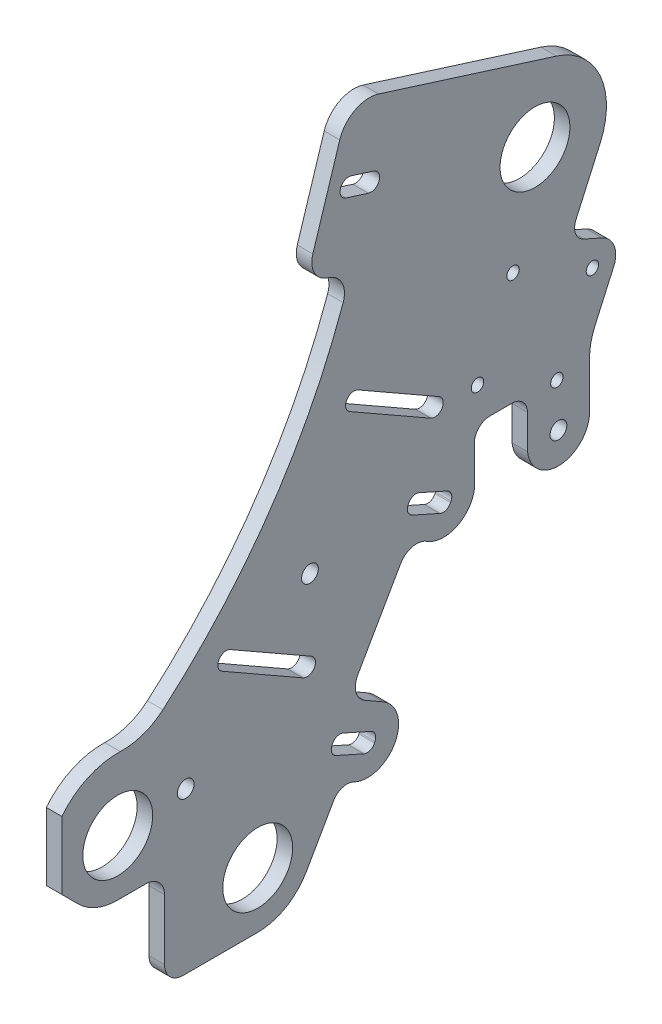
SolidWorks part; units mm, degrees
ref_plane "Front Plane" through (0, 0, 0) normal (0, 0, 1) x (1, 0, 0)
ref_plane "Top Plane" through (0, 0, 0) normal (0, 1, 0) x (1, 0, 0)
ref_plane "Right Plane" through (0, 0, 0) normal (1, 0, 0) x (0, 0, -1)
sketch "Sketch1" plane through (0, 0, 0) normal (1, 0, 0) x (0, 0, -1)
  line L0 (0, 0) -> (-57.2178, 40.0643) construction
  line L1 (55, 0) -> (-55, 0) construction
  line L2 (0, 0) -> (113.3671, 198.5091) construction
  line L3 (113.3671, 198.5091) -> (49.679, 218.5899) construction
  line L4 (99.338, 182.3162) -> (24.13, 14.224) construction
  line L5 (30.5555, 28.5852) -> (30.3602, 28.1486)
  line L6 (36.1341, 219.132) -> (45.2183, 216.2678)
  line L7 (38.2727, 225.9148) -> (47.3569, 223.0506)
  line L8 (34.9378, 30.2582) -> (46.2714, 25.1873)
  line L9 (47.9444, 20.8051) -> (47.749, 20.3685)
  line L10 (43.3668, 18.6955) -> (32.0332, 23.7664)
  line L11 (104.397, 158.4994) -> (136.8574, 143.9792) construction
  line L12 (136.8574, 143.9792) -> (122.3372, 111.5188) construction
  line L14 (61.6761, 98.1406) -> (61.4807, 97.704)
  line L15 (66.0583, 99.8136) -> (77.3919, 94.7427)
  line L16 (79.0649, 90.3605) -> (78.8696, 89.9239)
  line L17 (74.4873, 88.2509) -> (63.1537, 93.3218)
  line L18 (72.429, 126.8253) -> (39.3441, 145.7198) construction
  line L19 (20.2106, 60.9985) -> (-12.8742, 79.893) construction
  line L20 (70.7285, 123.8476) -> (37.6436, 142.7421)
  line L21 (74.1295, 129.8029) -> (41.0446, 148.6974)
  line L22 (18.5101, 58.0208) -> (-14.5747, 76.9153)
  line L23 (122.3372, 111.5188) -> (89.8768, 126.039) construction
  line L24 (89.8768, 126.039) -> (104.397, 158.4994) construction
  line L25 (104.397, 158.4994) -> (122.3372, 111.5188) construction
  line L26 (21.9112, 63.9761) -> (-11.1737, 82.8706)
  circle A0 centre (0, 0) radius 14.2875
  circle A1 centre (-57.2178, 40.0643) radius 14.2875
  circle A2 centre (113.3671, 198.5091) radius 14.2875
  arc A3 (45.2183, 216.2678) -> (47.3569, 223.0506) centre (46.2876, 219.6592) ccw
  arc A4 (38.2727, 225.9148) -> (36.1341, 219.132) centre (37.2034, 222.5234) ccw
  arc A17 (46.2714, 25.1873) -> (47.9444, 20.8051) centre (44.9167, 22.1597) cw
  arc A18 (47.749, 20.3685) -> (43.3668, 18.6955) centre (44.7214, 21.7231) cw
  arc A19 (32.0332, 23.7664) -> (30.3602, 28.1486) centre (33.3878, 26.794) cw
  arc A20 (30.5555, 28.5852) -> (34.9378, 30.2582) centre (33.5831, 27.2306) cw
  arc A21 (74.4873, 88.2509) -> (78.8696, 89.9239) centre (75.842, 91.2785) ccw
  arc A22 (79.0649, 90.3605) -> (77.3919, 94.7427) centre (76.0373, 91.7151) ccw
  arc A23 (63.1537, 93.3218) -> (61.4807, 97.704) centre (64.5084, 96.3494) cw
  arc A24 (61.6761, 98.1406) -> (66.0583, 99.8136) centre (64.7037, 96.786) cw
  circle A25 centre (-29.4365, 42.7262) radius 3.429
  circle A26 centre (21.3635, 93.5262) radius 3.429
  circle A27 centre (122.9635, 93.5262) radius 3.429
  arc A28 (70.7285, 123.8476) -> (74.1295, 129.8029) centre (72.429, 126.8253) ccw
  arc A29 (41.0446, 148.6974) -> (37.6436, 142.7421) centre (39.3441, 145.7198) ccw
  circle A32 centre (104.397, 158.4994) radius 2.54
  circle A33 centre (136.8574, 143.9792) radius 2.54
  circle A34 centre (122.3372, 111.5188) radius 2.54
  circle A35 centre (89.8768, 126.039) radius 2.54
  arc A36 (18.5101, 58.0208) -> (21.9112, 63.9761) centre (20.2106, 60.9985) ccw
  arc A37 (-11.1737, 82.8706) -> (-14.5747, 76.9153) centre (-12.8742, 79.893) ccw
  point P30 (113.3671, 135.0091)
  point P36 (3.6682, 70.4457)
  point P44 (0, 0)
  point P45 (0, 0)
  point P47 (49.299, 23.8327)
  point P54 (29.0056, 25.121)
  point P57 (31.9101, 31.6128)
  point P62 (80.4195, 93.3881)
  point P65 (60.1261, 94.6764)
  point P68 (63.0307, 101.1682)
  point P78 (55.8866, 136.2725)
  dimension "D2" = 28.575
  dimension "D4" = 228.6
  dimension "D10" = 13.081
  dimension "D7" = 3.556
  dimension "D8" = 9.525
  dimension "D11" = 65.895
  dimension "D18" = 35.56
  dimension "D20" = 38.1
  dimension "D21" = 24.1
  dimension "D27" = 7.112
  dimension "D22" = 5.08
  dimension "D29" = 3.3168
  dimension "D30" = 6.858
  dimension "D33" = 6.858
  dimension "D36" = 6.858
  dimension "D40" = 3.429
  dimension "D25" = 3.429
  dimension "D26" = 50.8
  dimension "D1" = 35
  dimension "D3" = 69.85
  dimension "D5" = 60.27
  dimension "D6" = 17.5
  dimension "D9" = 66.7788
  dimension "D12" = 14.224
  dimension "D13" = 184.15
  dimension "D14" = 24.13
  dimension "D15" = 7.112
  dimension "D16" = 165.1
  dimension "D17" = 19.05
  dimension "D19" = 63.5
  dimension "D23" = 19.05
  dimension "D24" = 76.2
  dimension "D28" = 88.9
  dimension "D31" = 27.7812
  dimension "D32" = 2.6619
  dimension "D34" = 78.5812
  dimension "D35" = 53.4619
  dimension "D37" = 180.1812
  dimension "D38" = 53.4619
  dimension "D39" = 82.55
  dimension "D41" = 38.1
sketch "Sketch2" plane through (0, 0, 0) normal (1, 0, 0) x (0, 0, -1)
  line L1 (-80.0778, 30.5954) -> (-80.0778, 58.2479)
  line L2 (19.8509, -11.3367) -> (31.0118, 8.2063)
  line L3 (0, 0) -> (113.3671, 198.5091) construction
  line L9 (113.3671, 198.5091) -> (49.679, 218.5899) construction
  line L11 (49.4775, 249.281) -> (122.1507, 226.3672)
  line L12 (33.5463, 240.9877) -> (22.5477, 206.1046)
  line L13 (28.5188, 194.6341) -> (29.0827, 194.4563)
  line L14 (110.3329, 92.1997) -> (110.288, 92.1997)
  line L15 (88.5941, 92.1997) -> (88.5941, 106.1697)
  line L16 (110.288, 92.1997) -> (110.288, 106.1697)
  line L17 (103.938, 112.5197) -> (94.9441, 112.5197)
  line L18 (88.5941, 92.1997) -> (88.5941, 89.8131)
  line L19 (58.4048, 78.4274) -> (40.9124, 47.8643)
  line L20 (43.7407, 37.4658) -> (51.2253, 33.1821)
  line L23 (-38.1, 9.5843) -> (-38.1, -15.24)
  line L24 (-30.48, -22.86) -> (0, -22.86)
  line L25 (-57.2178, 17.2043) -> (-45.72, 17.2043)
  line L26 (-73.3822, 23.8999) -> (-80.0778, 30.5954)
  line L27 (104.397, 158.4994) -> (136.8574, 143.9792) construction
  line L28 (136.8574, 143.9792) -> (122.3372, 111.5188) construction
  line L29 (122.3372, 111.5188) -> (89.8768, 126.039) construction
  line L30 (89.8768, 126.039) -> (104.397, 158.4994) construction
  line L31 (104.397, 158.4994) -> (122.3372, 111.5188) construction
  line L32 (140.031, 186.5818) -> (130.1045, 164.3908)
  line L33 (140.7468, 152.6739) -> (133.3081, 156.0014)
  line L34 (145.5521, 140.0898) -> (137.8775, 122.9329)
  line L35 (135.6635, 93.5262) -> (135.6635, 112.5613)
  arc A1 (0, -22.86) -> (19.8509, -11.3367) centre (0, 0) ccw
  arc A2 (39.3228, 10.758) -> (51.2253, 33.1821) centre (44.9167, 22.1597) ccw
  arc A3 (69.1503, 81.0446) -> (88.5941, 89.8131) centre (76.0373, 91.7151) ccw
  arc A7 (31.0118, 8.2063) -> (39.3228, 10.758) centre (36.5259, 5.0572) cw
  arc A13 (140.031, 186.5818) -> (122.1507, 226.3672) centre (113.3671, 198.5091) ccw
  arc A15 (33.5463, 240.9877) -> (49.4775, 249.281) centre (45.6585, 237.1687) cw
  arc A16 (34.9451, 182.6622) -> (-38.7381, 75.3772) centre (-204.3307, 268.0513) cw
  arc A17 (-56.1886, 69.2562) -> (-80.0778, 58.2479) centre (-57.2178, 40.0643) ccw
  arc A18 (29.0827, 194.4563) -> (34.9451, 182.6622) centre (26.3331, 185.7355) cw
  arc A19 (22.5477, 206.1046) -> (28.5188, 194.6341) centre (31.2685, 203.3549) ccw
  arc A21 (-38.7381, 75.3772) -> (-56.1886, 69.2562) centre (-55.2938, 94.6404) cw
  arc A22 (110.3329, 92.1997) -> (135.6635, 93.5262) centre (122.9635, 93.5262) ccw
  arc A25 (110.288, 106.1697) -> (103.938, 112.5197) centre (103.938, 106.1697) ccw
  arc A26 (88.5941, 106.1697) -> (94.9441, 112.5197) centre (94.9441, 106.1697) cw
  arc A27 (58.4048, 78.4274) -> (69.1503, 81.0446) centre (65.0182, 74.6423) cw
  arc A28 (43.7407, 37.4658) -> (40.9124, 47.8643) centre (47.5258, 44.0792) cw
  arc A29 (-73.3822, 23.8999) -> (-57.2178, 17.2043) centre (-57.2178, 40.0643) ccw
  arc A30 (-30.48, -22.86) -> (-38.1, -15.24) centre (-30.48, -15.24) cw
  arc A31 (-38.1, 9.5843) -> (-45.72, 17.2043) centre (-45.72, 9.5843) ccw
  arc A32 (145.5521, 140.0898) -> (140.7468, 152.6739) centre (136.8574, 143.9792) ccw
  arc A34 (135.6635, 112.5613) -> (137.8775, 122.9329) centre (161.0635, 112.5613) cw
  arc A35 (133.3081, 156.0014) -> (130.1045, 164.3908) centre (135.901, 161.7979) cw
  point P24 (84.2401, 101.4107)
  point P25 (-38.1, -22.86)
  point P27 (71.8548, 79.7236)
  point P30 (46.1964, 34.7951)
  point P41 (110.288, 112.5197)
  point P46 (135.6635, 116.6623)
  point P49 (0, 0)
  point P62 (37.3653, 253.0999)
  point P66 (37.9664, 191.6553)
  point P69 (19.798, 197.3838)
  point P71 (88.5941, 112.5197)
  point P74 (-48.0067, 67.784)
  point P86 (113.3671, 135.0091)
  point P92 (37.1273, 41.2509)
  dimension "D2" = 45.72
  dimension "D4" = 25.4
  dimension "D5" = 21.6939
  dimension "D6" = 38.1
  dimension "D7" = 19.05
  dimension "D8" = 25.4
  dimension "D9" = 6.35
  dimension "D10" = 6.35
  dimension "D11" = 58.42
  dimension "D15" = 12.7
  dimension "D17" = 9.144
  dimension "D18" = 254.0555
  dimension "D19" = 2.3866
  dimension "D20" = 25.4
  dimension "D21" = 25.4
  dimension "D28" = 6.35
  dimension "D30" = 7.62
  dimension "D31" = 7.62
  dimension "D33" = 22.86
  dimension "D34" = 29.21
  dimension "D35" = 7.62
  dimension "D3" = 22.86
  dimension "D12" = 88.9
  dimension "D14" = 58.42
  dimension "D16" = 19.05
  dimension "D22" = 180.1812
  dimension "D23" = 53.4619
  dimension "D25" = 20.32
  dimension "D26" = 20.32
  dimension "D27" = 12.6305
  dimension "D29" = 16.2437
  dimension "D32" = 35.2148
  dimension "D36" = 9.4689
  dimension "D37" = 35.56
  dimension "D38" = 63.5
  dimension "D39" = 24.1
extrude "Boss-Extrude1" add sketch "Sketch2" along normal blind 3.175 and the other way blind 3.175
extrude "Cut-Extrude1" cut sketch "Sketch1" against normal through all and the other way through all
